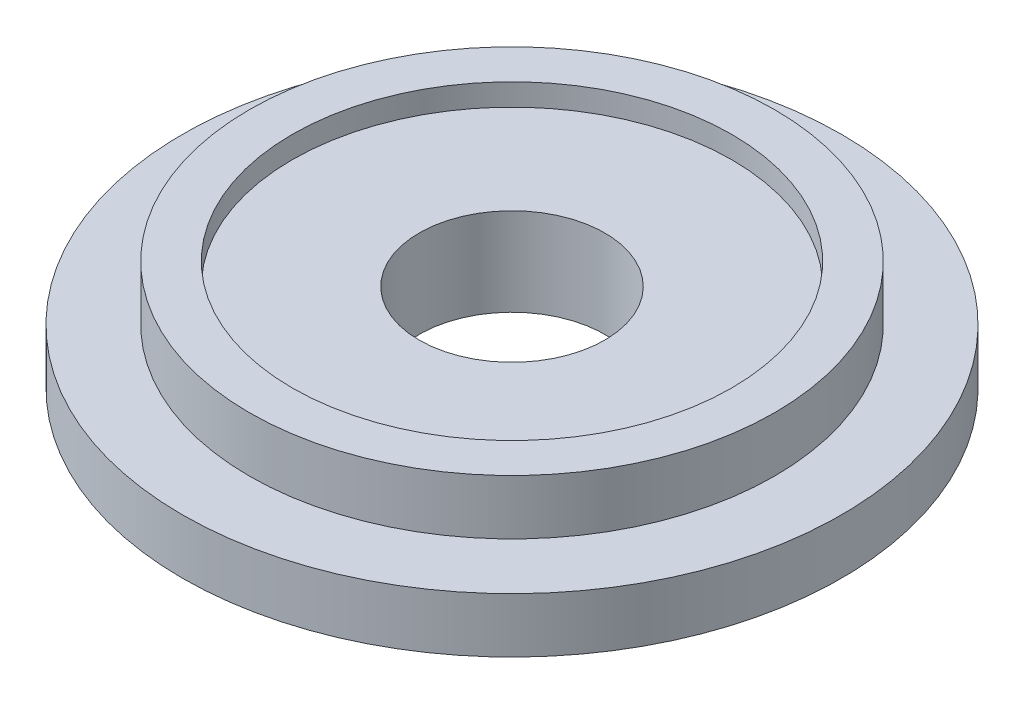
SolidWorks part; units mm, degrees
ref_plane "Front Plane" through (0, 0, 0) normal (0, 0, 1) x (1, 0, 0)
ref_plane "Top Plane" through (0, 0, 0) normal (0, 1, 0) x (1, 0, 0)
ref_plane "Right Plane" through (0, 0, 0) normal (1, 0, 0) x (0, 0, -1)
sketch "Croquis1" plane through (0, 0, 0) normal (0, 1, 0) x (1, 0, 0)
  circle A0 centre (0, 0) radius 23.9
  circle A1 centre (0, 0) radius 30
  circle A2 centre (0, 0) radius 8.45
  dimension "D1" = 47.8
  dimension "D2" = 60
  dimension "D3" = 16.9
extrude "Saliente-Extruir1" add sketch "Croquis1" along normal blind 5 contours A0 A2 region at (-23.224, 0, 0)
extrude "Saliente-Extruir2" add sketch "Croquis1<3>" against normal blind 5 contours A1 A0 | A0 A2 region at (-23.224, 0, 0) region at (-29.1515, 0, 0)
sketch "Croquis1<3>" plane through (0, 0, 0) normal (0, 1, 0) x (1, 0, 0) same geometry as "Croquis1"
sketch "Croquis2" plane through (0, 5, 0) normal (0, 1, 0) x (1, 0, 0)
  circle A0 centre (0, 0) radius 20
  dimension "D1" = 40
extrude "Cortar-Extruir1" cut sketch "Croquis2" against normal blind 2
equation "\"ID\"= 47.8"
equation "\"D1@Croquis1\"=\"ID\""
equation "\"OD\"= 60"
equation "\"D2@Croquis1\"=\"OD\""
equation "\"Dmandril\"=16.9"
equation "\"D3@Croquis1\"=\"Dmandril\""
